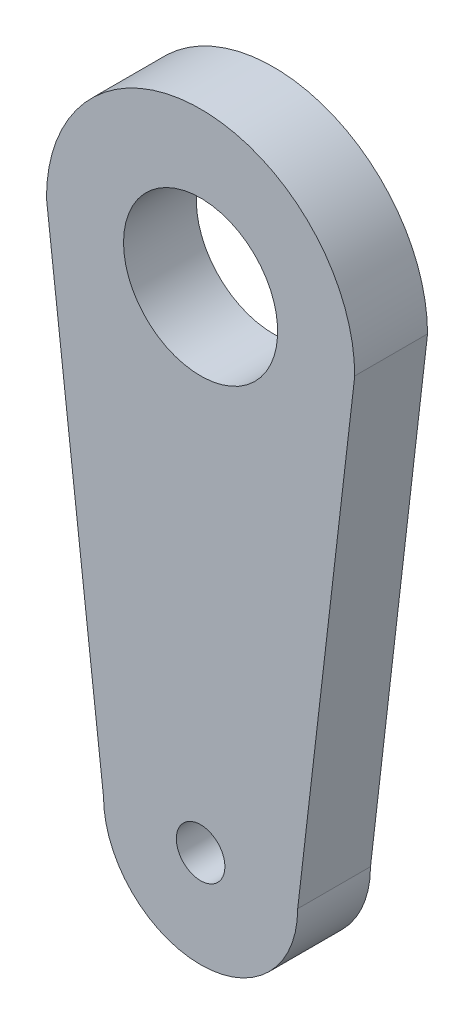
SolidWorks part; units mm, degrees
ref_plane "Front Plane" through (0, 0, 0) normal (0, 0, 1) x (1, 0, 0)
ref_plane "Top Plane" through (0, 0, 0) normal (0, 1, 0) x (1, 0, 0)
ref_plane "Right Plane" through (0, 0, 0) normal (1, 0, 0) x (0, 0, -1)
sketch "Sketch1" plane through (0, 0, 0) normal (0, 0, 1) x (1, 0, 0)
  line L1 (-6.35, 0) -> (6.35, 0)
  line L2 (-6.35, 0) -> (-4, -20.1837)
  line L3 (-4, -20.1837) -> (4, -20.1837)
  line L4 (6.35, 0) -> (4, -20.1837)
  arc A1 (6.35, 0) -> (-6.35, 0) centre (0, 0) ccw
  arc A2 (-4, -20.1837) -> (4, -20.1837) centre (0, -20.1837) ccw
  circle A3 centre (0, 0) radius 3.175
  circle A4 centre (0, -20.1837) radius 1
  point P5 (0, 0)
  dimension "D2" = 6.35
  dimension "D3" = 2
  dimension "D1" = 20.32
  dimension "D4" = 12.7
  dimension "D5" = 8
extrude "Boss-Extrude1" add sketch "Sketch1" along normal mid plane 2.9997 contours A4 L3 L4 L1 A3 L2 | A3 L1 A1 | A4 L3 A2 region at (0, 3.317, 0) region at (0, -9.9024, 0) region at (0, -21.9662, 0)
equation "\"pin hole\"= 2mm"
equation "\"dowel thick\"= 1 / 4"
equation "\"ply thick\"= 3mm"
equation "\"extend length\"= 0.8"
equation "\"D1@Sketch1\"=\"extend length\""
equation "\"D2@Sketch1\"=\"dowel thick\""
equation "\"D3@Sketch1\"=\"pin hole\""
equation "\"D4@Sketch1\"=\"dowel thick\"*2"
equation "\"D5@Sketch1\"=\"pin hole\"*4"
equation "\"D1@Boss-Extrude1\"=\"ply thick\""
